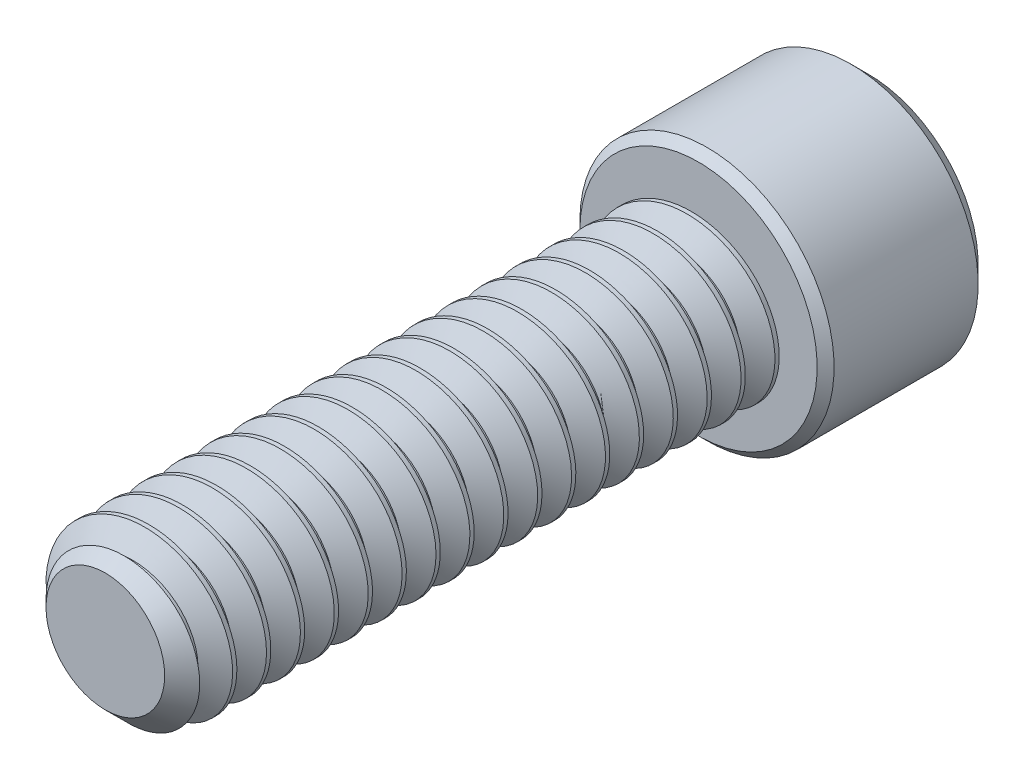
SolidWorks part; units mm, degrees
ref_plane "Front Plane" through (0, 0, 0) normal (0, 0, 1) x (1, 0, 0)
ref_plane "Top Plane" through (0, 0, 0) normal (0, 1, 0) x (1, 0, 0)
ref_plane "Right Plane" through (0, 0, 0) normal (1, 0, 0) x (0, 0, -1)
sketch "Sketch1" plane through (0, 0, 0) normal (0, 0, 1) x (1, 0, 0)
  line L0 (0, 3.175) -> (0, -3.175) construction
  circle A0 centre (0, 0) radius 3.175
  dimension "OD" = 6.35
extrude "Extrude1" add sketch "Sketch1" against normal blind 22.225
sketch "Sketch2" plane through (0, 0, 0) normal (0, 0, 1) x (1, 0, 0)
  circle A0 centre (0, 0) radius 3.175 construction
  circle A1 centre (0, 0) radius 3.175
curve "Helix/Spiral1" pitch 1.27 height 23.495 turns 18.5 parameters "pitch"=1.27
chamfer "Chamfer3" distance 0.9525 angle 45 1 edges at (3.175, 0, 0)
sketch "Sketch3" plane through (0, 0, 0) normal (1, 0, 0) x (0, 0, -1)
  line L0 (-1.1113, 3.175) -> (-0.635, 2.3501)
  line L1 (-0.635, 2.3501) -> (-0.4763, 2.3501)
  line L2 (-0.4763, 2.3501) -> (0, 3.175)
  line L3 (-1.1113, 3.175) -> (0, 3.175)
  line L4 (-0.5556, 3.175) -> (-0.5556, 2.3501) construction
  line L5 (-0.8731, 2.7626) -> (-0.2381, 2.7626) construction
  line L6 (0, 3.175) -> (0, -3.175) construction
  dimension "D1" = 0.1588
  dimension "D2" = 0.635
  dimension "D3" = 60
sweep "Cut-Sweep1" cut profiles "Sketch3" path "Helix/Spiral1"
sketch "Sketch6" plane through (0, 0, -22.225) normal (0, 0, -1) x (-1, 0, 0)
  circle A0 centre (0, 0) radius 4.7625
  dimension "head dia" = 9.525
extrude "Extrude2" add sketch "Sketch6" along normal blind 6.35
sketch "Sketch7" plane through (0, 0, -28.575) normal (0, 0, -1) x (-1, 0, 0)
  line L1 (0, 2.7496) -> (-2.3813, 1.3748)
  line L2 (-2.3813, 1.3748) -> (-2.3813, -1.3748)
  line L3 (-2.3813, -1.3748) -> (0, -2.7496)
  line L4 (0, -2.7496) -> (2.3813, -1.3748)
  line L5 (2.3813, -1.3748) -> (2.3813, 1.3748)
  line L6 (2.3813, 1.3748) -> (0, 2.7496)
  circle A0 centre (0, 0) radius 2.3813 construction
  dimension "hex dia" = 4.7625
extrude "Cut-Extrude1" cut sketch "Sketch7" against normal blind 3.5719
sketch "Sketch8" plane through (0, 0, -28.575) normal (0, 0, -1) x (-1, 0, 0)
  circle A0 centre (0, 0) radius 2.7496
extrude "Cut-Extrude2" cut sketch "Sketch8" against normal blind 0.635 draft 45
chamfer "Chamfer1" distance 0.635 angle 45 1 edges at (-4.7625, 0, -28.575)
chamfer "Chamfer2" distance 0.3175 angle 45 1 edges at (-4.7625, 0, -22.225)
sketch "Sketch9" plane through (0, 0, 0) normal (1, 0, 0) x (0, 0, -1)
  line L0 (0, 3.175) -> (0, -3.175) construction
  line L1 (6.985, 3.175) -> (6.985, -3.175) construction
  line L2 (22.225, 4.7625) -> (22.225, -4.7625) construction
  line L3 (28.575, 4.7625) -> (28.575, -4.7625) construction
  line L4 (28.575, 0) -> (0, 0) construction
  dimension "D1" = 6.985
  dimension "D2" = 6.35
  dimension "D3" = 9.525
  dimension "D4" = 22.225
equation "\"D3@Helix/Spiral1\" = \"screw length@Extrude1\"+\"pitch@Helix/Spiral1\""
equation "\"D1@Sketch3\" = \"pitch@Helix/Spiral1\"*.125"
equation "\"D2@Sketch3\" = \"pitch@Helix/Spiral1\"*.5"
equation "\"D1@Cut-Extrude1\" = \"hex dia@Sketch7\"*.75"
equation "\"D1@Chamfer1\" = \"head depth@Extrude2\"/10"
equation "\"D1@Sketch9\" = \"pitch@Helix/Spiral1\"*5.5"
equation "\"D1@Chamfer2\" = \"D1@Chamfer1\"/2"
equation "\"D1@Cut-Extrude2\" = \"D1@Chamfer2\"*2"
equation "\"D1@Chamfer3\" = \"pitch@Helix/Spiral1\"*.750"
equation "\"D2@Sketch9\" = \"head depth@Extrude2\""
equation "\"D3@Sketch9\" = \"head dia@Sketch6\""
equation "\"D4@Sketch9\" = \"screw length@Extrude1\""
